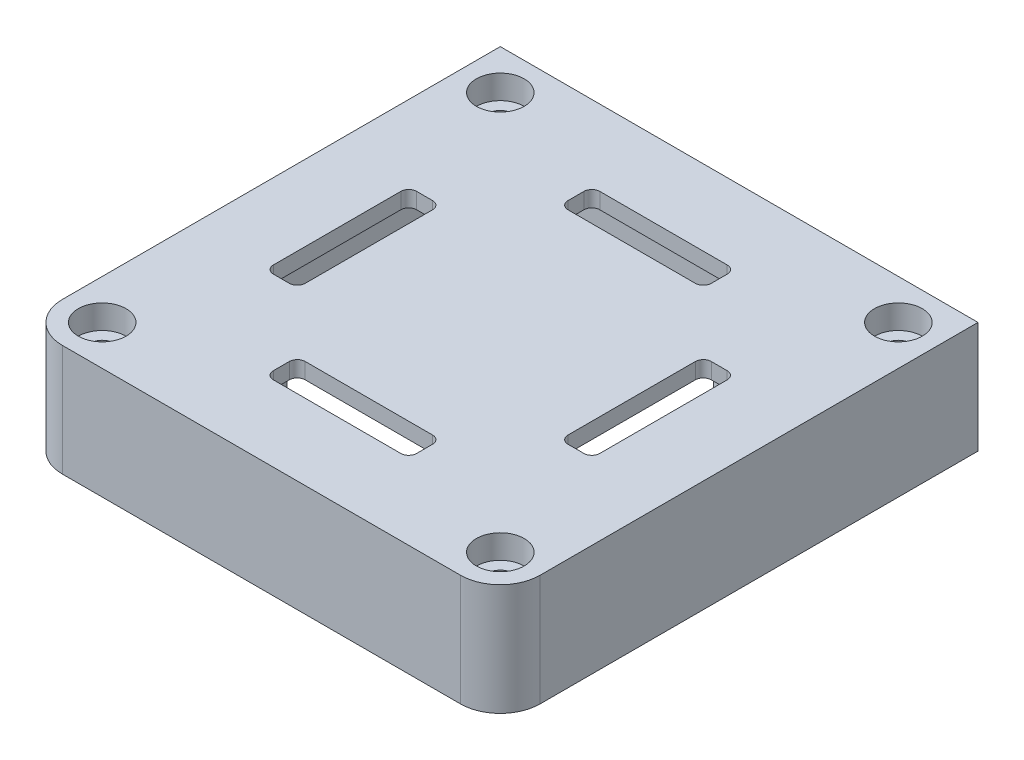
SolidWorks part; units mm, degrees
material "ABS"
ref_plane "Front Plane" through (0, 0, 0) normal (0, 0, 1) x (1, 0, 0)
ref_plane "Top Plane" through (0, 0, 0) normal (0, 1, 0) x (1, 0, 0)
ref_plane "Right Plane" through (0, 0, 0) normal (1, 0, 0) x (0, 0, -1)
other "Configuration Table"
sketch "Sketch1" plane through (0, 0, 0) normal (0, 1, 0) x (1, 0, 0)
  line L1 (-30, -30) -> (30, -30)
  line L2 (-30, -30) -> (-30, 30)
  line L3 (-30, 30) -> (30, 30)
  line L4 (30, -30) -> (30, 30)
  line L5 (-30, -30) -> (30, 30) construction
  line L6 (-30, 30) -> (30, -30) construction
  point P0 (0, 0)
  dimension "D1" = 60
extrude "Boss-Extrude1" add sketch "Sketch1" along normal blind 14
sketch "Sketch2" plane through (0, 14, 0) normal (0, 1, 0) x (1, 0, 0)
  line L1 (25, -25) -> (-25, -25) construction
  line L2 (25, -25) -> (25, 25) construction
  line L3 (25, 25) -> (-25, 25) construction
  line L4 (-25, -25) -> (-25, 25) construction
  line L5 (25, -25) -> (-25, 25) construction
  line L6 (25, 25) -> (-25, -25) construction
  circle A0 centre (-25, 25) radius 1.5
  circle A1 centre (-25, -25) radius 1.5
  circle A2 centre (25, -25) radius 1.5
  circle A3 centre (25, 25) radius 1.5
  point P0 (0, 0)
  dimension "D2" = 3
  dimension "D3" = 3
  dimension "D4" = 3
  dimension "D5" = 3
  dimension "D1" = 50
extrude "Cut-Extrude1" cut sketch "Sketch2" against normal blind 42
sketch "Sketch3" plane through (0, 14, 0) normal (0, 1, 0) x (1, 0, 0)
  circle A0 centre (-25, 25) radius 3
  circle A1 centre (-25, -25) radius 3
  circle A2 centre (25, -25) radius 3
  circle A3 centre (25, 25) radius 3
  dimension "D1" = 6
  dimension "D2" = 6
  dimension "D3" = 6
  dimension "D4" = 6
extrude "Cut-Extrude2" cut sketch "Sketch3" against normal blind 3
sketch "Sketch4" plane through (0, 0, 0) normal (0, -1, 0) x (1, 0, 0)
  line L1 (22.5, -22.5) -> (-22.5, -22.5)
  line L2 (22.5, -22.5) -> (22.5, 22.5)
  line L3 (22.5, 22.5) -> (-22.5, 22.5)
  line L4 (-22.5, -22.5) -> (-22.5, 22.5)
  line L5 (22.5, -22.5) -> (-22.5, 22.5) construction
  line L6 (22.5, 22.5) -> (-22.5, -22.5) construction
  point P0 (0, 0)
  dimension "D1" = 45
extrude "Cut-Extrude3" cut sketch "Sketch4" against normal blind 12
sketch "Sketch5" plane through (0, 12, 0) normal (0, -1, 0) x (1, 0, 0)
  line L0 (-22.5, -22.5) -> (22.5, -22.5) construction
  line L1 (9, 16.5) -> (-9, 16.5)
  line L2 (9, 16.5) -> (9, 20.5)
  line L3 (9, 20.5) -> (-9, 20.5)
  line L4 (-9, 16.5) -> (-9, 20.5)
  line L5 (9, 16.5) -> (-9, 20.5) construction
  line L6 (9, 20.5) -> (-9, 16.5) construction
  line L7 (9, -20.5) -> (-9, -20.5)
  line L8 (9, -20.5) -> (9, -16.5)
  line L9 (9, -16.5) -> (-9, -16.5)
  line L10 (-9, -20.5) -> (-9, -16.5)
  line L11 (9, -20.5) -> (-9, -16.5) construction
  line L12 (9, -16.5) -> (-9, -20.5) construction
  line L13 (22.5, 22.5) -> (-22.5, 22.5) construction
  line L14 (-30, -30) -> (-30, 30) construction
  line L15 (30, 30) -> (30, -30) construction
  line L16 (-22.5, 22.5) -> (-22.5, -22.5) construction
  line L17 (-20.5, -9) -> (-16.5, -9)
  line L18 (-20.5, -9) -> (-20.5, 9)
  line L19 (-20.5, 9) -> (-16.5, 9)
  line L20 (-16.5, -9) -> (-16.5, 9)
  line L21 (-20.5, -9) -> (-16.5, 9) construction
  line L22 (-20.5, 9) -> (-16.5, -9) construction
  line L23 (16.5, -9) -> (20.5, -9)
  line L24 (16.5, -9) -> (16.5, 9)
  line L25 (16.5, 9) -> (20.5, 9)
  line L26 (20.5, -9) -> (20.5, 9)
  line L27 (16.5, -9) -> (20.5, 9) construction
  line L28 (16.5, 9) -> (20.5, -9) construction
  line L29 (22.5, -22.5) -> (22.5, 22.5) construction
  line L30 (-30, 30) -> (30, 30) construction
  line L31 (-30, 30) -> (30, 30) construction
  point P0 (0, 18.5)
  point P5 (0, -18.5)
  point P18 (-18.5, 0)
  point P23 (18.5, 0)
  dimension "D1" = 4
  dimension "D2" = 18
  dimension "D3" = 4
  dimension "D4" = 18
  dimension "D5" = 2
  dimension "D6" = 2
  dimension "D7" = 21
  dimension "D8" = 21
  dimension "D9" = 21
  dimension "D10" = 18
  dimension "D11" = 4
  dimension "D12" = 18
  dimension "D13" = 4
  dimension "D14" = 2
  dimension "D15" = 2
  dimension "D16" = 21
  dimension "D17" = 21
extrude "Cut-Extrude4" cut sketch "Sketch5" against normal blind 7
sketch "Sketch6" plane through (0, 12, 0) normal (0, -1, 0) x (1, 0, 0)
  line L0 (0, -6) -> (0, 6) construction
  circle A0 centre (0, 6) radius 2.5
  circle A1 centre (0, -6) radius 2.5
  point P4 (0, 0)
  dimension "D1" = 5
  dimension "D2" = 5
extrude "Boss-Extrude2" add sketch "Sketch6" along normal blind 2.5
sketch "Sketch7" plane through (0, 9.5, 0) normal (0, -1, 0) x (1, 0, 0)
  circle A0 centre (0, 6) radius 1.5
  circle A1 centre (0, -6) radius 1.5
  dimension "D1" = 3
  dimension "D2" = 3
extrude "Cut-Extrude5" cut sketch "Sketch7" against normal blind 4
fillet "Fillet1" radius 2.5 2 edges at (0, 12, 3.5) (0, 12, -8.5)
sketch "Sketch8" plane through (0, 12, 0) normal (0, -1, 0) x (1, 0, 0)
  line L1 (15.5, -15.5) -> (-15.5, -15.5) construction
  line L2 (15.5, -15.5) -> (15.5, 15.5) construction
  line L3 (15.5, 15.5) -> (-15.5, 15.5) construction
  line L4 (-15.5, -15.5) -> (-15.5, 15.5) construction
  line L5 (15.5, -15.5) -> (-15.5, 15.5) construction
  line L6 (15.5, 15.5) -> (-15.5, -15.5) construction
  circle A0 centre (-15.5, 15.5) radius 3
  circle A1 centre (15.5, 15.5) radius 3
  circle A2 centre (15.5, -15.5) radius 3
  circle A3 centre (-15.5, -15.5) radius 3
  point P0 (0, 0)
  dimension "D2" = 6
  dimension "D3" = 6
  dimension "D4" = 6
  dimension "D5" = 6
  dimension "D1" = 31
extrude "Boss-Extrude3" add sketch "Sketch8" along normal blind 5
fillet "Fillet2" radius 2.5 4 edges at (-15.5, 12, -18.5) (15.5, 12, -18.5) (15.5, 12, 12.5) (-15.5, 12, 12.5)
sketch "Sketch9" plane through (0, 7, 0) normal (0, -1, 0) x (1, 0, 0)
  circle A0 centre (-15.5, 15.5) radius 2
  circle A1 centre (-15.5, -15.5) radius 2
  circle A2 centre (15.5, -15.5) radius 2
  circle A3 centre (15.5, 15.5) radius 2
  dimension "D1" = 4
  dimension "D2" = 4
  dimension "D3" = 4
  dimension "D4" = 4
extrude "Cut-Extrude6" cut sketch "Sketch9" against normal blind 5
fillet "Fillet3" radius 1 16 edges at (-9, 13, -16.5) (-9, 13, -20.5) (9, 13, -16.5) (9, 13, -20.5) (9, 13, 16.5) (9, 13, 20.5) (-9, 13, 16.5) (-9, 13, 20.5) (20.5, 13, 9) (16.5, 13, 9) (16.5, 13, -9) (20.5, 13, -9) (-16.5, 13, -9) (-20.5, 13, -9) (-16.5, 13, 9) (-20.5, 13, 9)
fillet "Fillet4" radius 6 4 edges at (-22.5, 6, -22.5) (22.5, 6, -22.5) (22.5, 6, 22.5) (-22.5, 6, 22.5)
fillet "Fillet5" radius 5 2 edges at (-30, 7, 30) (30, 7, 30)
